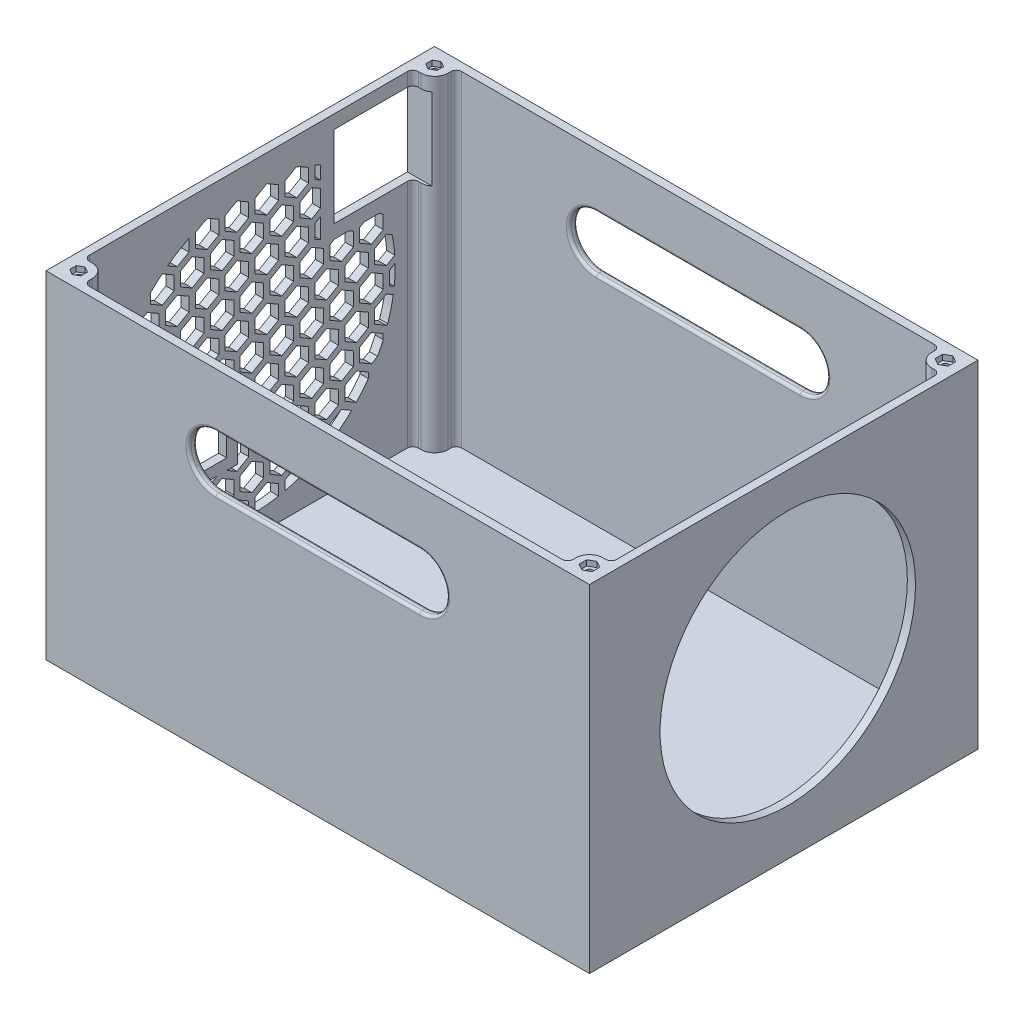
SolidWorks part; units mm, degrees
ref_plane "Front Plane" through (0, 0, 0) normal (0, 0, 1) x (1, 0, 0)
ref_plane "Top Plane" through (0, 0, 0) normal (0, 1, 0) x (1, 0, 0)
ref_plane "Right Plane" through (0, 0, 0) normal (1, 0, 0) x (0, 0, -1)
sketch "Sketch1" plane through (0, 0, 0) normal (0, 0, 1) x (1, 0, 0)
  line L1 (0, 0) -> (254, 0)
  line L2 (0, 0) -> (0, 152.4)
  line L3 (0, 152.4) -> (254, 152.4)
  line L4 (254, 0) -> (254, 152.4)
  dimension "D1" = 152.4
  dimension "D2" = 254
extrude "Boss-Extrude1" add sketch "Sketch1" along normal blind 3.81
sketch "Sketch2" plane through (0, 152.4, 0) normal (0, 1, 0) x (1, 0, 0)
  line L0 (254, 0) -> (0, 0) construction
  line L1 (0, -3.81) -> (0, 0) construction
  line L4 (127, 0) -> (127, -8.0453) construction
  line L11 (13.97, -7.62) -> (13.97, 0)
  line L12 (13.97, 0) -> (2.54, 0)
  line L14 (7.62, -13.97) -> (2.54, -13.97)
  line L21 (2.54, 0) -> (0, 0)
  line L22 (0, 0) -> (0, -13.97)
  line L23 (0, -13.97) -> (2.54, -13.97)
  line L24 (254, -13.97) -> (251.46, -13.97)
  line L25 (254, 0) -> (254, -13.97)
  line L26 (254, 0) -> (240.03, 0)
  line L27 (246.38, -13.97) -> (251.46, -13.97)
  line L29 (240.03, -7.62) -> (240.03, 0)
  circle A0 centre (7.62, -7.62) radius 1.5875
  arc A4 (7.62, -13.97) -> (13.97, -7.62) centre (7.62, -7.62) ccw
  arc A7 (246.38, -13.97) -> (240.03, -7.62) centre (246.38, -7.62) cw
  circle A8 centre (246.38, -7.62) radius 1.5875
  dimension "D1" = 3.175
  dimension "D2" = 7.62
  dimension "D3" = 7.62
  dimension "D4" = 12.7
extrude "Boss-Extrude2" add sketch "Sketch2" against normal through all
sketch "Sketch4" plane through (0, 0, 3.81) normal (0, 0, 1) x (1, 0, 0)
  line L5 (13.97, 0) -> (240.03, 0) construction
  line L10 (0, 152.4) -> (3.81, 152.4)
  line L11 (0, 152.4) -> (0, 0)
  line L12 (0, 0) -> (3.81, 0)
  line L13 (3.81, 152.4) -> (3.81, 0)
  line L15 (254, 152.4) -> (250.19, 152.4)
  line L16 (254, 152.4) -> (254, 0)
  line L17 (254, 0) -> (250.19, 0)
  line L18 (250.19, 152.4) -> (250.19, 0)
  dimension "D1" = 3.81
  dimension "D2" = 3.81
extrude "Boss-Extrude3" add sketch "Sketch4" along normal blind 177.8
sketch "Sketch3" plane through (0, 152.4, 0) normal (0, 1, 0) x (1, 0, 0)
  line L0 (127, 0) -> (127, -10.4452) construction
  line L1 (254, 0) -> (0, 0) construction
  circle A0 centre (7.62, -7.62) radius 1.7145
  circle A1 centre (246.38, -7.62) radius 1.7145
  dimension "D1" = 3.429
  dimension "D2" = 3.429
extrude "Cut-Extrude1" cut sketch "Sketch3" against normal through all
sketch "Sketch5" plane through (3.81, 0, 0) normal (1, 0, 0) x (0, 0, -1)
  line L5 (-181.61, 0) -> (-13.97, 0) construction
  line L6 (-181.61, 152.4) -> (-177.8, 152.4)
  line L7 (-181.61, 152.4) -> (-181.61, 0)
  line L8 (-181.61, 0) -> (-177.8, 0)
  line L9 (-177.8, 152.4) -> (-177.8, 0)
  dimension "D1" = 3.81
extrude "Boss-Extrude4" add sketch "Sketch5" along normal blind 248.92
sketch "Sketch6" plane through (0, 152.4, 0) normal (0, 1, 0) x (1, 0, 0)
  line L1 (7.62, -167.64) -> (0, -167.64)
  line L2 (0, -181.61) -> (0, 0) construction
  line L3 (127, -181.61) -> (127, -160.2672) construction
  line L4 (240.03, -181.61) -> (240.03, -173.99)
  line L5 (0, -167.64) -> (0, -181.61)
  line L6 (0, -181.61) -> (13.97, -181.61)
  line L7 (254, -181.61) -> (0, -181.61) construction
  line L8 (13.97, -181.61) -> (13.97, -173.99)
  line L9 (254, -181.61) -> (240.03, -181.61)
  line L10 (254, -167.64) -> (254, -181.61)
  line L11 (246.38, -167.64) -> (254, -167.64)
  circle A0 centre (7.62, -173.99) radius 1.5875
  arc A2 (13.97, -173.99) -> (7.62, -167.64) centre (7.62, -173.99) ccw
  arc A5 (240.03, -173.99) -> (246.38, -167.64) centre (246.38, -173.99) cw
  circle A6 centre (246.38, -173.99) radius 1.5875
  dimension "D1" = 7.62
  dimension "D2" = 7.62
  dimension "D3" = 3.175
  dimension "D4" = 12.7
extrude "Boss-Extrude5" add sketch "Sketch6" against normal through all
sketch "Sketch8" plane through (254, 0, 0) normal (1, 0, 0) x (0, 0, -1)
  line L1 (-181.61, 0) -> (0, 0) construction
  line L2 (0, 0) -> (0, 152.4) construction
  circle A0 centre (-88.9, 76.2) radius 59.69
  dimension "D1" = 119.38
  dimension "D2" = 76.2
  dimension "D3" = 88.9
extrude "Cut-Extrude3" cut sketch "Sketch8" against normal blind 5.08
sketch "Sketch9" plane through (0, 0, 0) normal (-1, 0, 0) x (0, 0, 1)
  line L1 (0, 152.4) -> (0, 0) construction
  line L14 (54.2537, 127.1602) -> (59.7529, 130.3352)
  line L15 (59.7529, 130.3352) -> (59.7529, 136.1667)
  line L19 (49.4362, 129.9416) -> (54.2537, 127.1602)
  line L20 (68.2237, 127.1602) -> (73.7229, 130.3352)
  line L21 (73.7229, 130.3352) -> (73.7229, 136.6852)
  line L22 (73.7229, 136.6852) -> (68.5258, 139.6858)
  line L23 (67.0955, 139.2089) -> (62.7244, 136.6852)
  line L24 (62.7244, 136.6852) -> (62.7244, 130.3352)
  line L25 (62.7244, 130.3352) -> (68.2237, 127.1602)
  line L26 (82.1937, 127.1602) -> (87.6929, 130.3352)
  line L27 (87.6929, 130.3352) -> (87.6929, 136.6852)
  line L28 (87.6929, 136.6852) -> (82.1937, 139.8602)
  line L29 (82.1937, 139.8602) -> (76.6944, 136.6852)
  line L30 (76.6944, 136.6852) -> (76.6944, 130.3352)
  line L31 (76.6944, 130.3352) -> (82.1937, 127.1602)
  line L32 (96.1637, 127.1602) -> (101.6629, 130.3352)
  line L33 (101.6629, 130.3352) -> (101.6629, 136.6852)
  line L34 (101.6629, 136.6852) -> (96.1637, 139.8602)
  line L35 (96.1637, 139.8602) -> (90.6644, 136.6852)
  line L36 (90.6644, 136.6852) -> (90.6644, 130.3352)
  line L37 (90.6644, 130.3352) -> (96.1637, 127.1602)
  line L38 (110.1337, 127.1602) -> (115.6329, 130.3352)
  line L39 (115.6329, 130.3352) -> (115.6329, 136.6852)
  line L40 (115.6329, 136.6852) -> (112.1801, 138.6787)
  line L41 (109.6312, 139.5701) -> (104.6344, 136.6852)
  line L42 (104.6344, 136.6852) -> (104.6344, 130.3352)
  line L43 (104.6344, 130.3352) -> (110.1337, 127.1602)
  line L44 (124.1037, 127.1602) -> (128.6085, 129.7611)
  line L48 (118.6044, 135.8926) -> (118.6044, 130.3352)
  line L49 (118.6044, 130.3352) -> (124.1037, 127.1602)
  line L80 (35.777, 116.4927) -> (38.7979, 118.2369)
  line L81 (38.7979, 118.2369) -> (38.7979, 120.1925)
  line L86 (47.2687, 115.0619) -> (52.7679, 118.2369)
  line L87 (52.7679, 118.2369) -> (52.7679, 124.5869)
  line L88 (52.7679, 124.5869) -> (47.2687, 127.7619)
  line L89 (47.2687, 127.7619) -> (45.2349, 126.5877)
  line L90 (41.7694, 123.3621) -> (41.7694, 118.2369)
  line L91 (41.7694, 118.2369) -> (47.2687, 115.0619)
  line L92 (61.2387, 115.0619) -> (66.7379, 118.2369)
  line L93 (66.7379, 118.2369) -> (66.7379, 124.5869)
  line L94 (66.7379, 124.5869) -> (61.2387, 127.7619)
  line L95 (61.2387, 127.7619) -> (55.7394, 124.5869)
  line L96 (55.7394, 124.5869) -> (55.7394, 118.2369)
  line L97 (55.7394, 118.2369) -> (61.2387, 115.0619)
  line L98 (75.2087, 115.0619) -> (80.7079, 118.2369)
  line L99 (80.7079, 118.2369) -> (80.7079, 124.5869)
  line L100 (80.7079, 124.5869) -> (75.2087, 127.7619)
  line L101 (75.2087, 127.7619) -> (69.7094, 124.5869)
  line L102 (69.7094, 124.5869) -> (69.7094, 118.2369)
  line L103 (69.7094, 118.2369) -> (75.2087, 115.0619)
  line L104 (89.1787, 115.0619) -> (94.6779, 118.2369)
  line L105 (94.6779, 118.2369) -> (94.6779, 124.5869)
  line L106 (94.6779, 124.5869) -> (89.1787, 127.7619)
  line L107 (89.1787, 127.7619) -> (83.6794, 124.5869)
  line L108 (83.6794, 124.5869) -> (83.6794, 118.2369)
  line L109 (83.6794, 118.2369) -> (89.1787, 115.0619)
  line L110 (103.1487, 115.0619) -> (108.6479, 118.2369)
  line L111 (108.6479, 118.2369) -> (108.6479, 124.5869)
  line L112 (108.6479, 124.5869) -> (103.1487, 127.7619)
  line L113 (103.1487, 127.7619) -> (97.6494, 124.5869)
  line L114 (97.6494, 124.5869) -> (97.6494, 118.2369)
  line L115 (97.6494, 118.2369) -> (103.1487, 115.0619)
  line L116 (117.1187, 115.0619) -> (122.6179, 118.2369)
  line L117 (122.6179, 118.2369) -> (122.6179, 124.5869)
  line L118 (122.6179, 124.5869) -> (117.1187, 127.7619)
  line L119 (117.1187, 127.7619) -> (111.6194, 124.5869)
  line L120 (111.6194, 124.5869) -> (111.6194, 118.2369)
  line L121 (111.6194, 118.2369) -> (117.1187, 115.0619)
  line L122 (131.0887, 115.0619) -> (136.5879, 118.2369)
  line L123 (136.5879, 118.2369) -> (136.5879, 122.7984)
  line L124 (131.3681, 127.6005) -> (131.0887, 127.7619)
  line L125 (131.0887, 127.7619) -> (125.5894, 124.5869)
  line L126 (125.5894, 124.5869) -> (125.5894, 118.2369)
  line L127 (125.5894, 118.2369) -> (131.0887, 115.0619)
  line L132 (139.5594, 119.5495) -> (139.5594, 118.2369)
  line L133 (139.5594, 118.2369) -> (141.5799, 117.0704)
  line L152 (28.3651, 104.1479) -> (31.8129, 106.1385)
  line L153 (31.8129, 106.1385) -> (31.8129, 110.6474)
  line L158 (40.2837, 102.9635) -> (45.7829, 106.1385)
  line L159 (45.7829, 106.1385) -> (45.7829, 112.4885)
  line L160 (45.7829, 112.4885) -> (40.2837, 115.6635)
  line L161 (40.2837, 115.6635) -> (34.7844, 112.4885)
  line L162 (34.7844, 112.4885) -> (34.7844, 106.1385)
  line L163 (34.7844, 106.1385) -> (40.2837, 102.9635)
  line L164 (54.2537, 102.9635) -> (59.7529, 106.1385)
  line L165 (59.7529, 106.1385) -> (59.7529, 112.4885)
  line L166 (59.7529, 112.4885) -> (54.2537, 115.6635)
  line L167 (54.2537, 115.6635) -> (48.7544, 112.4885)
  line L168 (48.7544, 112.4885) -> (48.7544, 106.1385)
  line L169 (48.7544, 106.1385) -> (54.2537, 102.9635)
  line L170 (68.2237, 102.9635) -> (73.7229, 106.1385)
  line L171 (73.7229, 106.1385) -> (73.7229, 112.4885)
  line L172 (73.7229, 112.4885) -> (68.2237, 115.6635)
  line L173 (68.2237, 115.6635) -> (62.7244, 112.4885)
  line L174 (62.7244, 112.4885) -> (62.7244, 106.1385)
  line L175 (62.7244, 106.1385) -> (68.2237, 102.9635)
  line L176 (82.1937, 102.9635) -> (87.6929, 106.1385)
  line L177 (87.6929, 106.1385) -> (87.6929, 112.4885)
  line L178 (87.6929, 112.4885) -> (82.1937, 115.6635)
  line L179 (82.1937, 115.6635) -> (76.6944, 112.4885)
  line L180 (76.6944, 112.4885) -> (76.6944, 106.1385)
  line L181 (76.6944, 106.1385) -> (82.1937, 102.9635)
  line L182 (96.1637, 102.9635) -> (101.6629, 106.1385)
  line L183 (101.6629, 106.1385) -> (101.6629, 112.4885)
  line L184 (101.6629, 112.4885) -> (96.1637, 115.6635)
  line L185 (96.1637, 115.6635) -> (90.6644, 112.4885)
  line L186 (90.6644, 112.4885) -> (90.6644, 106.1385)
  line L187 (90.6644, 106.1385) -> (96.1637, 102.9635)
  line L188 (110.1337, 102.9635) -> (115.6329, 106.1385)
  line L189 (115.6329, 106.1385) -> (115.6329, 112.4885)
  line L190 (115.6329, 112.4885) -> (110.1337, 115.6635)
  line L191 (110.1337, 115.6635) -> (104.6344, 112.4885)
  line L192 (104.6344, 112.4885) -> (104.6344, 106.1385)
  line L193 (104.6344, 106.1385) -> (110.1337, 102.9635)
  line L194 (124.1037, 102.9635) -> (129.6029, 106.1385)
  line L195 (129.6029, 106.1385) -> (129.6029, 112.4885)
  line L196 (129.6029, 112.4885) -> (124.1037, 115.6635)
  line L197 (124.1037, 115.6635) -> (118.6044, 112.4885)
  line L198 (118.6044, 112.4885) -> (118.6044, 106.1385)
  line L199 (118.6044, 106.1385) -> (124.1037, 102.9635)
  line L200 (138.0737, 102.9635) -> (143.5729, 106.1385)
  line L201 (143.5729, 106.1385) -> (143.5729, 112.4885)
  line L202 (143.5729, 112.4885) -> (138.0737, 115.6635)
  line L203 (138.0737, 115.6635) -> (132.5744, 112.4885)
  line L204 (132.5744, 112.4885) -> (132.5744, 106.1385)
  line L205 (132.5744, 106.1385) -> (138.0737, 102.9635)
  line L210 (146.5444, 109.7064) -> (146.5444, 106.1385)
  line L211 (146.5444, 106.1385) -> (149.2297, 104.5882)
  line L224 (24.6234, 93.922) -> (24.8279, 94.0401)
  line L225 (24.8279, 94.0401) -> (24.8279, 94.648)
  line L230 (33.2987, 90.8651) -> (38.7979, 94.0401)
  line L231 (38.7979, 94.0401) -> (38.7979, 100.3901)
  line L232 (38.7979, 100.3901) -> (33.2987, 103.5651)
  line L233 (33.2987, 103.5651) -> (27.7994, 100.3901)
  line L234 (27.7994, 100.3901) -> (27.7994, 94.0401)
  line L235 (27.7994, 94.0401) -> (33.2987, 90.8651)
  line L236 (47.2687, 90.8651) -> (52.7679, 94.0401)
  line L237 (52.7679, 94.0401) -> (52.7679, 100.3901)
  line L238 (52.7679, 100.3901) -> (47.2687, 103.5651)
  line L239 (47.2687, 103.5651) -> (41.7694, 100.3901)
  line L240 (41.7694, 100.3901) -> (41.7694, 94.0401)
  line L241 (41.7694, 94.0401) -> (47.2687, 90.8651)
  line L242 (61.2387, 90.8651) -> (66.7379, 94.0401)
  line L243 (66.7379, 94.0401) -> (66.7379, 100.3901)
  line L244 (66.7379, 100.3901) -> (61.2387, 103.5651)
  line L245 (61.2387, 103.5651) -> (55.7394, 100.3901)
  line L246 (55.7394, 100.3901) -> (55.7394, 94.0401)
  line L247 (55.7394, 94.0401) -> (61.2387, 90.8651)
  line L248 (75.2087, 90.8651) -> (80.7079, 94.0401)
  line L249 (80.7079, 94.0401) -> (80.7079, 100.3901)
  line L250 (80.7079, 100.3901) -> (75.2087, 103.5651)
  line L251 (75.2087, 103.5651) -> (69.7094, 100.3901)
  line L252 (69.7094, 100.3901) -> (69.7094, 94.0401)
  line L253 (69.7094, 94.0401) -> (75.2087, 90.8651)
  line L254 (89.1787, 90.8651) -> (94.6779, 94.0401)
  line L255 (94.6779, 94.0401) -> (94.6779, 100.3901)
  line L256 (94.6779, 100.3901) -> (89.1787, 103.5651)
  line L257 (89.1787, 103.5651) -> (83.6794, 100.3901)
  line L258 (83.6794, 100.3901) -> (83.6794, 94.0401)
  line L259 (83.6794, 94.0401) -> (89.1787, 90.8651)
  line L260 (103.1487, 90.8651) -> (108.6479, 94.0401)
  line L261 (108.6479, 94.0401) -> (108.6479, 100.3901)
  line L262 (108.6479, 100.3901) -> (103.1487, 103.5651)
  line L263 (103.1487, 103.5651) -> (97.6494, 100.3901)
  line L264 (97.6494, 100.3901) -> (97.6494, 94.0401)
  line L265 (97.6494, 94.0401) -> (103.1487, 90.8651)
  line L266 (117.1187, 90.8651) -> (122.6179, 94.0401)
  line L267 (122.6179, 94.0401) -> (122.6179, 100.3901)
  line L268 (122.6179, 100.3901) -> (117.1187, 103.5651)
  line L269 (117.1187, 103.5651) -> (111.6194, 100.3901)
  line L270 (111.6194, 100.3901) -> (111.6194, 94.0401)
  line L271 (111.6194, 94.0401) -> (117.1187, 90.8651)
  line L272 (131.0887, 90.8651) -> (136.5879, 94.0401)
  line L273 (136.5879, 94.0401) -> (136.5879, 100.3901)
  line L274 (136.5879, 100.3901) -> (131.0887, 103.5651)
  line L275 (131.0887, 103.5651) -> (125.5894, 100.3901)
  line L276 (125.5894, 100.3901) -> (125.5894, 94.0401)
  line L277 (125.5894, 94.0401) -> (131.0887, 90.8651)
  line L278 (145.0587, 90.8651) -> (150.5579, 94.0401)
  line L279 (150.5579, 94.0401) -> (150.5579, 100.3901)
  line L280 (150.5579, 100.3901) -> (145.0587, 103.5651)
  line L281 (145.0587, 103.5651) -> (139.5594, 100.3901)
  line L282 (139.5594, 100.3901) -> (139.5594, 94.0401)
  line L283 (139.5594, 94.0401) -> (145.0587, 90.8651)
  line L302 (26.3137, 78.7667) -> (31.8129, 81.9417)
  line L303 (31.8129, 81.9417) -> (31.8129, 88.2917)
  line L304 (31.8129, 88.2917) -> (26.3137, 91.4667)
  line L305 (26.3137, 91.4667) -> (23.6543, 89.9313)
  line L307 (22.3999, 81.0264) -> (26.3137, 78.7667)
  line L308 (40.2837, 78.7667) -> (45.7829, 81.9417)
  line L309 (45.7829, 81.9417) -> (45.7829, 88.2917)
  line L310 (45.7829, 88.2917) -> (40.2837, 91.4667)
  line L311 (40.2837, 91.4667) -> (34.7844, 88.2917)
  line L312 (34.7844, 88.2917) -> (34.7844, 81.9417)
  line L313 (34.7844, 81.9417) -> (40.2837, 78.7667)
  line L314 (54.2537, 78.7667) -> (59.7529, 81.9417)
  line L315 (59.7529, 81.9417) -> (59.7529, 88.2917)
  line L316 (59.7529, 88.2917) -> (54.2537, 91.4667)
  line L317 (54.2537, 91.4667) -> (48.7544, 88.2917)
  line L318 (48.7544, 88.2917) -> (48.7544, 81.9417)
  line L319 (48.7544, 81.9417) -> (54.2537, 78.7667)
  line L320 (68.2237, 78.7667) -> (73.7229, 81.9417)
  line L321 (73.7229, 81.9417) -> (73.7229, 88.2917)
  line L322 (73.7229, 88.2917) -> (68.2237, 91.4667)
  line L323 (68.2237, 91.4667) -> (62.7244, 88.2917)
  line L324 (62.7244, 88.2917) -> (62.7244, 81.9417)
  line L325 (62.7244, 81.9417) -> (68.2237, 78.7667)
  line L326 (82.1937, 78.7667) -> (87.6929, 81.9417)
  line L327 (87.6929, 81.9417) -> (87.6929, 88.2917)
  line L328 (87.6929, 88.2917) -> (82.1937, 91.4667)
  line L329 (82.1937, 91.4667) -> (76.6944, 88.2917)
  line L330 (76.6944, 88.2917) -> (76.6944, 81.9417)
  line L331 (76.6944, 81.9417) -> (82.1937, 78.7667)
  line L332 (96.1637, 78.7667) -> (101.6629, 81.9417)
  line L333 (101.6629, 81.9417) -> (101.6629, 88.2917)
  line L334 (101.6629, 88.2917) -> (96.1637, 91.4667)
  line L335 (96.1637, 91.4667) -> (90.6644, 88.2917)
  line L336 (90.6644, 88.2917) -> (90.6644, 81.9417)
  line L337 (90.6644, 81.9417) -> (96.1637, 78.7667)
  line L338 (110.1337, 78.7667) -> (115.6329, 81.9417)
  line L339 (115.6329, 81.9417) -> (115.6329, 88.2917)
  line L340 (115.6329, 88.2917) -> (110.1337, 91.4667)
  line L341 (110.1337, 91.4667) -> (104.6344, 88.2917)
  line L342 (104.6344, 88.2917) -> (104.6344, 81.9417)
  line L343 (104.6344, 81.9417) -> (110.1337, 78.7667)
  line L344 (124.1037, 78.7667) -> (129.6029, 81.9417)
  line L345 (129.6029, 81.9417) -> (129.6029, 88.2917)
  line L346 (129.6029, 88.2917) -> (124.1037, 91.4667)
  line L347 (124.1037, 91.4667) -> (118.6044, 88.2917)
  line L348 (118.6044, 88.2917) -> (118.6044, 81.9417)
  line L349 (118.6044, 81.9417) -> (124.1037, 78.7667)
  line L350 (138.0737, 78.7667) -> (143.5729, 81.9417)
  line L351 (143.5729, 81.9417) -> (143.5729, 88.2917)
  line L352 (143.5729, 88.2917) -> (138.0737, 91.4667)
  line L353 (138.0737, 91.4667) -> (132.5744, 88.2917)
  line L354 (132.5744, 88.2917) -> (132.5744, 81.9417)
  line L355 (132.5744, 81.9417) -> (138.0737, 78.7667)
  line L356 (152.0437, 78.7667) -> (155.4218, 80.7171)
  line L358 (154.0674, 90.2983) -> (152.0437, 91.4667)
  line L359 (152.0437, 91.4667) -> (146.5444, 88.2917)
  line L360 (146.5444, 88.2917) -> (146.5444, 81.9417)
  line L361 (146.5444, 81.9417) -> (152.0437, 78.7667)
  line L374 (22.6605, 68.592) -> (24.8279, 69.8434)
  line L375 (24.8279, 69.8434) -> (24.8279, 76.1934)
  line L376 (24.8279, 76.1934) -> (22.2416, 77.6866)
  line L380 (33.2987, 66.6684) -> (38.7979, 69.8434)
  line L381 (38.7979, 69.8434) -> (38.7979, 76.1934)
  line L382 (38.7979, 76.1934) -> (33.2987, 79.3684)
  line L383 (33.2987, 79.3684) -> (27.7994, 76.1934)
  line L384 (27.7994, 76.1934) -> (27.7994, 69.8434)
  line L385 (27.7994, 69.8434) -> (33.2987, 66.6684)
  line L386 (47.2687, 66.6684) -> (52.7679, 69.8434)
  line L387 (52.7679, 69.8434) -> (52.7679, 76.1934)
  line L388 (52.7679, 76.1934) -> (47.2687, 79.3684)
  line L389 (47.2687, 79.3684) -> (41.7694, 76.1934)
  line L390 (41.7694, 76.1934) -> (41.7694, 69.8434)
  line L391 (41.7694, 69.8434) -> (47.2687, 66.6684)
  line L392 (61.2387, 66.6684) -> (66.7379, 69.8434)
  line L393 (66.7379, 69.8434) -> (66.7379, 76.1934)
  line L394 (66.7379, 76.1934) -> (61.2387, 79.3684)
  line L395 (61.2387, 79.3684) -> (55.7394, 76.1934)
  line L396 (55.7394, 76.1934) -> (55.7394, 69.8434)
  line L397 (55.7394, 69.8434) -> (61.2387, 66.6684)
  line L398 (75.2087, 66.6684) -> (80.7079, 69.8434)
  line L399 (80.7079, 69.8434) -> (80.7079, 76.1934)
  line L400 (80.7079, 76.1934) -> (75.2087, 79.3684)
  line L401 (75.2087, 79.3684) -> (69.7094, 76.1934)
  line L402 (69.7094, 76.1934) -> (69.7094, 69.8434)
  line L403 (69.7094, 69.8434) -> (75.2087, 66.6684)
  line L404 (89.1787, 66.6684) -> (94.6779, 69.8434)
  line L405 (94.6779, 69.8434) -> (94.6779, 76.1934)
  line L406 (94.6779, 76.1934) -> (89.1787, 79.3684)
  line L407 (89.1787, 79.3684) -> (83.6794, 76.1934)
  line L408 (83.6794, 76.1934) -> (83.6794, 69.8434)
  line L409 (83.6794, 69.8434) -> (89.1787, 66.6684)
  line L410 (103.1487, 66.6684) -> (108.6479, 69.8434)
  line L411 (108.6479, 69.8434) -> (108.6479, 76.1934)
  line L412 (108.6479, 76.1934) -> (103.1487, 79.3684)
  line L413 (103.1487, 79.3684) -> (97.6494, 76.1934)
  line L414 (97.6494, 76.1934) -> (97.6494, 69.8434)
  line L415 (97.6494, 69.8434) -> (103.1487, 66.6684)
  line L416 (117.1187, 66.6684) -> (122.6179, 69.8434)
  line L417 (122.6179, 69.8434) -> (122.6179, 76.1934)
  line L418 (122.6179, 76.1934) -> (117.1187, 79.3684)
  line L419 (117.1187, 79.3684) -> (111.6194, 76.1934)
  line L420 (111.6194, 76.1934) -> (111.6194, 69.8434)
  line L421 (111.6194, 69.8434) -> (117.1187, 66.6684)
  line L422 (131.0887, 66.6684) -> (136.5879, 69.8434)
  line L423 (136.5879, 69.8434) -> (136.5879, 76.1934)
  line L424 (136.5879, 76.1934) -> (131.0887, 79.3684)
  line L425 (131.0887, 79.3684) -> (125.5894, 76.1934)
  line L426 (125.5894, 76.1934) -> (125.5894, 69.8434)
  line L427 (125.5894, 69.8434) -> (131.0887, 66.6684)
  line L428 (145.0587, 66.6684) -> (150.5579, 69.8434)
  line L429 (150.5579, 69.8434) -> (150.5579, 76.1934)
  line L430 (150.5579, 76.1934) -> (145.0587, 79.3684)
  line L431 (145.0587, 79.3684) -> (139.5594, 76.1934)
  line L432 (139.5594, 76.1934) -> (139.5594, 69.8434)
  line L433 (139.5594, 69.8434) -> (145.0587, 66.6684)
  line L437 (155.5648, 77.3685) -> (153.5294, 76.1934)
  line L438 (153.5294, 76.1934) -> (153.5294, 69.8434)
  line L439 (153.5294, 69.8434) -> (155.1735, 68.8941)
  line L452 (26.3137, 54.57) -> (31.8129, 57.745)
  line L453 (31.8129, 57.745) -> (31.8129, 64.095)
  line L454 (31.8129, 64.095) -> (26.3137, 67.27)
  line L455 (26.3137, 67.27) -> (23.1028, 65.4162)
  line L457 (25.7132, 54.9167) -> (26.3137, 54.57)
  line L458 (40.2837, 54.57) -> (45.7829, 57.745)
  line L459 (45.7829, 57.745) -> (45.7829, 64.095)
  line L460 (45.7829, 64.095) -> (40.2837, 67.27)
  line L461 (40.2837, 67.27) -> (34.7844, 64.095)
  line L462 (34.7844, 64.095) -> (34.7844, 57.745)
  line L463 (34.7844, 57.745) -> (40.2837, 54.57)
  line L464 (54.2537, 54.57) -> (59.7529, 57.745)
  line L465 (59.7529, 57.745) -> (59.7529, 64.095)
  line L466 (59.7529, 64.095) -> (54.2537, 67.27)
  line L467 (54.2537, 67.27) -> (48.7544, 64.095)
  line L468 (48.7544, 64.095) -> (48.7544, 57.745)
  line L469 (48.7544, 57.745) -> (54.2537, 54.57)
  line L470 (68.2237, 54.57) -> (73.7229, 57.745)
  line L471 (73.7229, 57.745) -> (73.7229, 64.095)
  line L472 (73.7229, 64.095) -> (68.2237, 67.27)
  line L473 (68.2237, 67.27) -> (62.7244, 64.095)
  line L474 (62.7244, 64.095) -> (62.7244, 57.745)
  line L475 (62.7244, 57.745) -> (68.2237, 54.57)
  line L476 (82.1937, 54.57) -> (87.6929, 57.745)
  line L477 (87.6929, 57.745) -> (87.6929, 64.095)
  line L478 (87.6929, 64.095) -> (82.1937, 67.27)
  line L479 (82.1937, 67.27) -> (76.6944, 64.095)
  line L480 (76.6944, 64.095) -> (76.6944, 57.745)
  line L481 (76.6944, 57.745) -> (82.1937, 54.57)
  line L482 (96.1637, 54.57) -> (101.6629, 57.745)
  line L483 (101.6629, 57.745) -> (101.6629, 64.095)
  line L484 (101.6629, 64.095) -> (96.1637, 67.27)
  line L485 (96.1637, 67.27) -> (90.6644, 64.095)
  line L486 (90.6644, 64.095) -> (90.6644, 57.745)
  line L487 (90.6644, 57.745) -> (96.1637, 54.57)
  line L488 (110.1337, 54.57) -> (115.6329, 57.745)
  line L489 (115.6329, 57.745) -> (115.6329, 64.095)
  line L490 (115.6329, 64.095) -> (110.1337, 67.27)
  line L491 (110.1337, 67.27) -> (104.6344, 64.095)
  line L492 (104.6344, 64.095) -> (104.6344, 57.745)
  line L493 (104.6344, 57.745) -> (110.1337, 54.57)
  line L494 (124.1037, 54.57) -> (129.6029, 57.745)
  line L495 (129.6029, 57.745) -> (129.6029, 64.095)
  line L496 (129.6029, 64.095) -> (124.1037, 67.27)
  line L497 (124.1037, 67.27) -> (118.6044, 64.095)
  line L498 (118.6044, 64.095) -> (118.6044, 57.745)
  line L499 (118.6044, 57.745) -> (124.1037, 54.57)
  line L500 (138.0737, 54.57) -> (143.5729, 57.745)
  line L501 (143.5729, 57.745) -> (143.5729, 64.095)
  line L502 (143.5729, 64.095) -> (138.0737, 67.27)
  line L503 (138.0737, 67.27) -> (132.5744, 64.095)
  line L504 (132.5744, 64.095) -> (132.5744, 57.745)
  line L505 (132.5744, 57.745) -> (138.0737, 54.57)
  line L508 (154.7447, 65.7105) -> (152.0437, 67.27)
  line L509 (152.0437, 67.27) -> (146.5444, 64.095)
  line L510 (146.5444, 64.095) -> (146.5444, 57.745)
  line L511 (146.5444, 57.745) -> (152.0437, 54.57)
  line L530 (33.2987, 42.4716) -> (38.7979, 45.6466)
  line L531 (38.7979, 45.6466) -> (38.7979, 51.9966)
  line L532 (38.7979, 51.9966) -> (33.2987, 55.1716)
  line L533 (33.2987, 55.1716) -> (27.7994, 51.9966)
  line L534 (27.7994, 51.9966) -> (27.7994, 49.5115)
  line L535 (30.4526, 44.1148) -> (33.2987, 42.4716)
  line L536 (47.2687, 42.4716) -> (52.7679, 45.6466)
  line L537 (52.7679, 45.6466) -> (52.7679, 51.9966)
  line L538 (52.7679, 51.9966) -> (47.2687, 55.1716)
  line L539 (47.2687, 55.1716) -> (41.7694, 51.9966)
  line L540 (41.7694, 51.9966) -> (41.7694, 45.6466)
  line L541 (41.7694, 45.6466) -> (47.2687, 42.4716)
  line L542 (61.2387, 42.4716) -> (66.7379, 45.6466)
  line L543 (66.7379, 45.6466) -> (66.7379, 51.9966)
  line L544 (66.7379, 51.9966) -> (61.2387, 55.1716)
  line L545 (61.2387, 55.1716) -> (55.7394, 51.9966)
  line L546 (55.7394, 51.9966) -> (55.7394, 45.6466)
  line L547 (55.7394, 45.6466) -> (61.2387, 42.4716)
  line L548 (75.2087, 42.4716) -> (80.7079, 45.6466)
  line L549 (80.7079, 45.6466) -> (80.7079, 51.9966)
  line L550 (80.7079, 51.9966) -> (75.2087, 55.1716)
  line L551 (75.2087, 55.1716) -> (69.7094, 51.9966)
  line L552 (69.7094, 51.9966) -> (69.7094, 45.6466)
  line L553 (69.7094, 45.6466) -> (75.2087, 42.4716)
  line L554 (89.1787, 42.4716) -> (94.6779, 45.6466)
  line L555 (94.6779, 45.6466) -> (94.6779, 51.9966)
  line L556 (94.6779, 51.9966) -> (89.1787, 55.1716)
  line L557 (89.1787, 55.1716) -> (83.6794, 51.9966)
  line L558 (83.6794, 51.9966) -> (83.6794, 45.6466)
  line L559 (83.6794, 45.6466) -> (89.1787, 42.4716)
  line L560 (103.1487, 42.4716) -> (108.6479, 45.6466)
  line L561 (108.6479, 45.6466) -> (108.6479, 51.9966)
  line L562 (108.6479, 51.9966) -> (103.1487, 55.1716)
  line L563 (103.1487, 55.1716) -> (97.6494, 51.9966)
  line L564 (97.6494, 51.9966) -> (97.6494, 45.6466)
  line L565 (97.6494, 45.6466) -> (103.1487, 42.4716)
  line L566 (117.1187, 42.4716) -> (122.6179, 45.6466)
  line L567 (122.6179, 45.6466) -> (122.6179, 51.9966)
  line L568 (122.6179, 51.9966) -> (117.1187, 55.1716)
  line L569 (117.1187, 55.1716) -> (111.6194, 51.9966)
  line L570 (111.6194, 51.9966) -> (111.6194, 45.6466)
  line L571 (111.6194, 45.6466) -> (117.1187, 42.4716)
  line L572 (131.0887, 42.4716) -> (136.5879, 45.6466)
  line L573 (136.5879, 45.6466) -> (136.5879, 51.9966)
  line L574 (136.5879, 51.9966) -> (131.0887, 55.1716)
  line L575 (131.0887, 55.1716) -> (125.5894, 51.9966)
  line L576 (125.5894, 51.9966) -> (125.5894, 45.6466)
  line L577 (125.5894, 45.6466) -> (131.0887, 42.4716)
  line L578 (145.0587, 42.4716) -> (147.0851, 43.6416)
  line L579 (150.5579, 50.8257) -> (150.5579, 51.9966)
  line L580 (150.5579, 51.9966) -> (145.0587, 55.1716)
  line L581 (145.0587, 55.1716) -> (139.5594, 51.9966)
  line L582 (139.5594, 51.9966) -> (139.5594, 45.6466)
  line L583 (139.5594, 45.6466) -> (145.0587, 42.4716)
  line L608 (40.2837, 30.3732) -> (45.7829, 33.5482)
  line L609 (45.7829, 33.5482) -> (45.7829, 39.8982)
  line L610 (45.7829, 39.8982) -> (40.2837, 43.0732)
  line L611 (40.2837, 43.0732) -> (34.7844, 39.8982)
  line L612 (34.7844, 39.8982) -> (34.7844, 37.2505)
  line L614 (54.2537, 30.3732) -> (59.7529, 33.5482)
  line L615 (59.7529, 33.5482) -> (59.7529, 39.8982)
  line L616 (59.7529, 39.8982) -> (54.2537, 43.0732)
  line L617 (54.2537, 43.0732) -> (48.7544, 39.8982)
  line L618 (48.7544, 39.8982) -> (48.7544, 33.5482)
  line L619 (48.7544, 33.5482) -> (54.2537, 30.3732)
  line L620 (68.2237, 30.3732) -> (73.7229, 33.5482)
  line L621 (73.7229, 33.5482) -> (73.7229, 39.8982)
  line L622 (73.7229, 39.8982) -> (68.2237, 43.0732)
  line L623 (68.2237, 43.0732) -> (62.7244, 39.8982)
  line L624 (62.7244, 39.8982) -> (62.7244, 33.5482)
  line L625 (62.7244, 33.5482) -> (68.2237, 30.3732)
  line L626 (82.1937, 30.3732) -> (87.6929, 33.5482)
  line L627 (87.6929, 33.5482) -> (87.6929, 39.8982)
  line L628 (87.6929, 39.8982) -> (82.1937, 43.0732)
  line L629 (82.1937, 43.0732) -> (76.6944, 39.8982)
  line L630 (76.6944, 39.8982) -> (76.6944, 33.5482)
  line L631 (76.6944, 33.5482) -> (82.1937, 30.3732)
  line L632 (96.1637, 30.3732) -> (101.6629, 33.5482)
  line L633 (101.6629, 33.5482) -> (101.6629, 39.8982)
  line L634 (101.6629, 39.8982) -> (96.1637, 43.0732)
  line L635 (96.1637, 43.0732) -> (90.6644, 39.8982)
  line L636 (90.6644, 39.8982) -> (90.6644, 33.5482)
  line L637 (90.6644, 33.5482) -> (96.1637, 30.3732)
  line L638 (110.1337, 30.3732) -> (115.6329, 33.5482)
  line L639 (115.6329, 33.5482) -> (115.6329, 39.8982)
  line L640 (115.6329, 39.8982) -> (110.1337, 43.0732)
  line L641 (110.1337, 43.0732) -> (104.6344, 39.8982)
  line L642 (104.6344, 39.8982) -> (104.6344, 33.5482)
  line L643 (104.6344, 33.5482) -> (110.1337, 30.3732)
  line L644 (124.1037, 30.3732) -> (129.6029, 33.5482)
  line L645 (129.6029, 33.5482) -> (129.6029, 39.8982)
  line L646 (129.6029, 39.8982) -> (124.1037, 43.0732)
  line L647 (124.1037, 43.0732) -> (118.6044, 39.8982)
  line L648 (118.6044, 39.8982) -> (118.6044, 33.5482)
  line L649 (118.6044, 33.5482) -> (124.1037, 30.3732)
  line L651 (143.5729, 38.0369) -> (143.5729, 39.8982)
  line L652 (143.5729, 39.8982) -> (138.0737, 43.0732)
  line L653 (138.0737, 43.0732) -> (132.5744, 39.8982)
  line L654 (132.5744, 39.8982) -> (132.5744, 33.5482)
  line L655 (132.5744, 33.5482) -> (137.5918, 30.6515)
  line L686 (51.7272, 20.849) -> (52.7679, 21.4499)
  line L687 (52.7679, 21.4499) -> (52.7679, 27.7999)
  line L688 (52.7679, 27.7999) -> (47.2687, 30.9749)
  line L689 (47.2687, 30.9749) -> (42.563, 28.258)
  line L692 (61.2387, 18.2749) -> (66.7379, 21.4499)
  line L693 (66.7379, 21.4499) -> (66.7379, 27.7999)
  line L694 (66.7379, 27.7999) -> (61.2387, 30.9749)
  line L695 (61.2387, 30.9749) -> (55.7394, 27.7999)
  line L696 (55.7394, 27.7999) -> (55.7394, 21.4499)
  line L697 (55.7394, 21.4499) -> (61.2387, 18.2749)
  line L698 (75.2087, 18.2749) -> (80.7079, 21.4499)
  line L699 (80.7079, 21.4499) -> (80.7079, 27.7999)
  line L700 (80.7079, 27.7999) -> (75.2087, 30.9749)
  line L701 (75.2087, 30.9749) -> (69.7094, 27.7999)
  line L702 (69.7094, 27.7999) -> (69.7094, 21.4499)
  line L703 (69.7094, 21.4499) -> (75.2087, 18.2749)
  line L704 (89.1787, 18.2749) -> (94.6779, 21.4499)
  line L705 (94.6779, 21.4499) -> (94.6779, 27.7999)
  line L706 (94.6779, 27.7999) -> (89.1787, 30.9749)
  line L707 (89.1787, 30.9749) -> (83.6794, 27.7999)
  line L708 (83.6794, 27.7999) -> (83.6794, 21.4499)
  line L709 (83.6794, 21.4499) -> (89.1787, 18.2749)
  line L710 (103.1487, 18.2749) -> (108.6479, 21.4499)
  line L711 (108.6479, 21.4499) -> (108.6479, 27.7999)
  line L712 (108.6479, 27.7999) -> (103.1487, 30.9749)
  line L713 (103.1487, 30.9749) -> (97.6494, 27.7999)
  line L714 (97.6494, 27.7999) -> (97.6494, 21.4499)
  line L715 (97.6494, 21.4499) -> (103.1487, 18.2749)
  line L716 (117.1187, 18.2749) -> (122.6179, 21.4499)
  line L717 (122.6179, 21.4499) -> (122.6179, 27.7999)
  line L718 (122.6179, 27.7999) -> (117.1187, 30.9749)
  line L719 (117.1187, 30.9749) -> (111.6194, 27.7999)
  line L720 (111.6194, 27.7999) -> (111.6194, 21.4499)
  line L721 (111.6194, 21.4499) -> (117.1187, 18.2749)
  line L724 (135.4449, 28.4598) -> (131.0887, 30.9749)
  line L725 (131.0887, 30.9749) -> (125.5894, 27.7999)
  line L726 (125.5894, 27.7999) -> (125.5894, 21.4499)
  line L727 (125.5894, 21.4499) -> (126.3298, 21.0224)
  line L771 (73.7229, 11.2753) -> (73.7229, 15.7015)
  line L772 (73.7229, 15.7015) -> (68.2237, 18.8765)
  line L773 (68.2237, 18.8765) -> (62.7244, 15.7015)
  line L774 (62.7244, 15.7015) -> (62.7244, 14.8779)
  line L777 (87.6929, 9.3515) -> (87.6929, 15.7015)
  line L778 (87.6929, 15.7015) -> (82.1937, 18.8765)
  line L779 (82.1937, 18.8765) -> (76.6944, 15.7015)
  line L780 (76.6944, 15.7015) -> (76.6944, 10.6517)
  line L783 (101.6629, 10.7579) -> (101.6629, 15.7015)
  line L784 (101.6629, 15.7015) -> (96.1637, 18.8765)
  line L785 (96.1637, 18.8765) -> (90.6644, 15.7015)
  line L786 (90.6644, 15.7015) -> (90.6644, 9.3515)
  line L789 (115.6329, 15.1189) -> (115.6329, 15.7015)
  line L790 (115.6329, 15.7015) -> (110.1337, 18.8765)
  line L791 (110.1337, 18.8765) -> (104.6344, 15.7015)
  line L792 (104.6344, 15.7015) -> (104.6344, 11.4082)
  circle A0 centre (88.9, 76.2) radius 66.675
  dimension "D2" = 88.9
  dimension "D3" = 133.35
extrude "Cut-Extrude4" cut sketch "Sketch9" against normal blind 5.08 contours L96 L97 L92 L93 L94 L95 | L15 A0 L19 L14 | L22 A0 L23 L24 L25 L20 L21 | L30 L31 L26 L27 L28 L29 | L36 L37 L32 L33 L34 L35 | L40 A0 L41 L42 L43 L38 L39 | L44 A0 L48 L49 | L123 A0 L124 L125 L126 L127 L122 | L120 L121 L116 L117 L118 L119 | L114 L115 L110 L111 L112 L113 | L108 L109 L104 L105 L106 L107 | L102 L103 L98 L99 L100 L101 | L89 A0 L90 L91 L86 L87 L88 | L162 L163 L158 L159 L160 L161 | L153 A0 L152 | L168 L169 L164 L165 L166 L167 | L174 L175 L170 L171 L172 L173 | L180 L181 L176 L177 L178 L179 | L186 L187 L182 L183 L184 L185 | L192 L193 L188 L189 L190 L191 | L198 L199 L194 L195 L196 L197 | L204 L205 L200 L201 L202 L203 | L211 A0 L210 | L282 L283 L278 L279 L280 L281 | L276 L277 L272 L273 L274 L275 | L264 L265 L260 L261 L262 L263 | L258 L259 L254 L255 L256 L257 | L252 L253 L248 L249 L250 L251 | L246 L247 L242 L243 L244 L245 | L240 L241 L236 L237 L238 L239 | L234 L235 L230 L231 L232 L233 | L270 L271 L266 L267 L268 L269 | L356 A0 L358 L359 L360 L361 | L354 L355 L350 L351 L352 L353 | L348 L349 L344 L345 L346 L347 | L342 L343 L338 L339 L340 L341 | L336 L337 L332 L333 L334 L335 | L330 L331 L326 L327 L328 L329 | L324 L325 L320 L321 L322 L323 | L318 L319 L314 L315 L316 L317 | L312 L313 L308 L309 L310 L311 | L305 A0 L307 L302 L303 L304 | L384 L385 L380 L381 L382 L383 | L376 A0 L374 L375 | L390 L391 L386 L387 L388 L389 | L396 L397 L392 L393 L394 L395 | L402 L403 L398 L399 L400 L401 | L408 L409 L404 L405 L406 L407 | L414 L415 L410 L411 L412 L413 | L420 L421 L416 L417 L418 L419 | L426 L427 L422 L423 L424 L425 | L432 L433 L428 L429 L430 L431 | L439 A0 L437 L438 | L511 A0 L508 L509 L510 | L504 L505 L500 L501 L502 L503 | L498 L499 L494 L495 L496 L497 | L492 L493 L488 L489 L490 L491 | L689 A0 L686 L687 L688 | L727 A0 L724 L725 L726 | L792 A0 L789 L790 L791 | L786 A0 L783 L784 L785 | L780 A0 L777 L778 L779 | L774 A0 L771 L772 L773 | L720 L721 L716 L717 L718 L719 | L714 L715 L710 L711 L712 L713 | L708 L709 L704 L705 L706 L707 | L702 L703 L698 L699 L700 L701 | L486 L487 L482 L483 L484 L485 | L480 L481 L476 L477 L478 L479 | L474 L475 L470 L471 L472 L473 | L468 L469 L464 L465 L466 L467 | L552 L553 L548 L549 L550 L551 | L455 A0 L457 L452 L453 L454 | L534 A0 L535 L530 L531 L532 L533 | L540 L541 L536 L537 L538 L539 | L612 A0 L608 L609 L610 L611 | L618 L619 L614 L615 L616 L617 | L696 L697 L692 L693 L694 L695 | L578 A0 L579 L580 L581 L582 L583 | L655 A0 L651 L652 L653 L654 | L576 L577 L572 L573 L574 L575 | L648 L649 L644 L645 L646 L647 | L570 L571 L566 L567 L568 L569 | L642 L643 L638 L639 L640 L641 | L564 L565 L560 L561 L562 L563 | L636 L637 L632 L633 L634 L635 | L558 L559 L554 L555 L556 L557 | L462 L463 L458 L459 L460 L461 | L624 L625 L620 L621 L622 L623 | L630 L631 L626 L627 L628 L629 | L546 L547 L542 L543 L544 L545 region at (0, 131.2286, 55.6428) region at (0, 121.3456, 47.3535) region at (0, 133.4991, 68.2242) region at (0, 133.4782, 110.1309) region at (0, 107.0044, 30.6269) region at (0, 131.0949, 122.6123) region at (0, 121.2624, 130.9271) region at (0, 85.028, 27.0856) region at (0, 73.1739, 23.5093) region at (0, 106.8277, 147.462) region at (0, 61.2088, 27.6064) region at (0, 84.9994, 151.0338) region at (0, 48.9391, 33.5241) region at (0, 73.187, 154.545) region at (0, 37.0445, 40.6639) region at (0, 61.2995, 150.4908) region at (0, 26.3596, 48.7526) region at (0, 49.0085, 144.6788) region at (0, 15.0667, 68.9748) region at (0, 37.1727, 137.558) region at (0, 13.6643, 82.3326) region at (0, 26.4962, 129.4676) region at (0, 13.6929, 96.0118) region at (0, 15.1503, 109.326) region at (0, 133.5102, 82.1937) region at (0, 133.5102, 96.1637) region at (0, 121.4119, 61.2387) region at (0, 121.4119, 75.2087) region at (0, 121.4119, 89.1787) region at (0, 121.4119, 103.1487) region at (0, 121.4119, 117.1187) region at (0, 109.3135, 40.2837) region at (0, 109.3135, 54.2537) region at (0, 109.3135, 68.2237) region at (0, 109.3135, 82.1937) region at (0, 109.3135, 96.1637) region at (0, 109.3135, 110.1337) region at (0, 109.3135, 124.1037) region at (0, 109.3135, 138.0737) region at (0, 97.2151, 33.2987) region at (0, 97.2151, 47.2687) region at (0, 97.2151, 61.2387) region at (0, 97.2151, 75.2087) region at (0, 97.2151, 89.1787) region at (0, 97.2151, 103.1487) region at (0, 97.2151, 117.1187) region at (0, 97.2151, 131.0887) region at (0, 97.2151, 145.0587) region at (0, 85.1167, 40.2837) region at (0, 85.1167, 54.2537) region at (0, 85.1167, 68.2237) region at (0, 85.1167, 82.1937) region at (0, 85.1167, 96.1637) region at (0, 85.1167, 110.1337) region at (0, 85.1167, 124.1037) region at (0, 85.1167, 138.0737) region at (0, 73.0184, 33.2987) region at (0, 73.0184, 47.2687) region at (0, 73.0184, 61.2387) region at (0, 73.0184, 75.2087)
sketch "Sketch10" plane through (0, 0, 0) normal (-1, 0, 0) x (0, 0, 1)
  line L0 (103.1487, 66.6684) -> (108.6479, 69.8434) construction
  line L1 (148.4494, 38.2218) -> (100.9514, 38.2218)
  line L2 (148.4494, 38.2218) -> (148.4494, 65.3998)
  line L3 (148.4494, 65.3998) -> (100.9514, 65.3998)
  line L4 (100.9514, 38.2218) -> (100.9514, 65.3998)
  line L5 (131.0887, 55.1716) -> (125.5894, 51.9966) construction
  line L6 (95.8714, 33.1233) -> (153.5294, 33.1233)
  line L7 (95.8714, 33.1233) -> (95.8714, 69.8434)
  line L8 (95.8714, 69.8434) -> (153.5294, 69.8434)
  line L9 (153.5294, 33.1233) -> (153.5294, 69.8434)
  line L10 (95.8714, 33.1233) -> (153.5294, 69.8434) construction
  line L11 (95.8714, 69.8434) -> (153.5294, 33.1233) construction
  point P6 (124.7004, 51.4834)
  dimension "D1" = 27.178
  dimension "D2" = 47.498
  dimension "D3" = 5.08
  dimension "D4" = 5.08
extrude "Boss-Extrude6" add sketch "Sketch10" against normal blind 3.81
sketch "Sketch11" plane through (0, 0, 0) normal (-1, 0, 0) x (0, 0, 1)
  line L1 (100.9514, 38.2218) -> (148.4494, 38.2218)
  line L2 (100.9514, 38.2218) -> (100.9514, 65.1948)
  line L3 (100.9514, 65.1948) -> (148.4494, 65.1948)
  line L4 (148.4494, 38.2218) -> (148.4494, 65.1948)
  dimension "D1" = 26.9731
  dimension "D2" = 47.498
extrude "Cut-Extrude5" cut sketch "Sketch11" against normal blind 7.62
fillet "Fillet1" radius 2.54 8 edges at (3.81, 76.2, 13.97) (13.97, 76.2, 3.81) (13.97, 76.2, 177.8) (3.81, 76.2, 167.64) (250.19, 76.2, 167.64) (240.03, 76.2, 177.8) (240.03, 76.2, 3.81) (250.19, 76.2, 13.97)
sketch "Sketch12" plane through (0, 0, 0) normal (-1, 0, 0) x (0, 0, 1)
  line L1 (100.9514, 65.1948) -> (148.4494, 65.1948)
  line L2 (100.9514, 65.1948) -> (100.9514, 65.4488)
  line L3 (100.9514, 65.4488) -> (148.4494, 65.4488)
  line L4 (148.4494, 65.1948) -> (148.4494, 65.4488)
  dimension "D1" = 0.254
extrude "Cut-Extrude6" cut sketch "Sketch12" against normal blind 7.62
sketch "Sketch13" plane through (0, 0, 0) normal (-1, 0, 0) x (0, 0, 1)
  line L0 (122.6179, 69.8434) -> (111.6194, 69.8434) construction
  line L1 (114.9214, 69.8434) -> (133.9714, 69.8434)
  line L2 (114.9214, 69.8434) -> (114.9214, 82.5434)
  line L3 (114.9214, 82.5434) -> (133.9714, 82.5434)
  line L4 (133.9714, 69.8434) -> (133.9714, 82.5434)
  line L6 (100.9514, 65.4488) -> (100.9514, 38.2218) construction
  line L9 (133.3104, 33.1233) -> (139.7916, 33.1233) construction
  line L10 (133.9714, 33.1233) -> (114.9214, 33.1233)
  line L11 (133.9714, 33.1233) -> (133.9714, 20.4233)
  line L12 (133.9714, 20.4233) -> (114.9214, 20.4233)
  line L13 (114.9214, 33.1233) -> (114.9214, 20.4233)
  dimension "D1" = 19.05
  dimension "D2" = 12.7
  dimension "D3" = 13.97
  dimension "D4" = 19.05
  dimension "D5" = 12.7
  dimension "D6" = 13.97
extrude "Boss-Extrude9" add sketch "Sketch13" against normal blind 3.81
sketch "Sketch15" plane through (0, 0, 0) normal (-1, 0, 0) x (0, 0, 1)
  line L0 (181.61, 152.4) -> (0, 152.4) construction
  line L1 (12.7, 146.05) -> (50.8, 146.05)
  line L2 (12.7, 146.05) -> (12.7, 107.95)
  line L3 (12.7, 107.95) -> (50.8, 107.95)
  line L4 (50.8, 146.05) -> (50.8, 107.95)
  line L5 (0, 152.4) -> (0, 0) construction
  dimension "D1" = 38.1
  dimension "D2" = 38.1
  dimension "D3" = 44.45
  dimension "D4" = 50.8
extrude "Cut-Extrude8" cut sketch "Sketch15" against normal blind 12.7
sketch "Sketch16" plane through (0, 0, 0) normal (-1, 0, 0) x (0, 0, 1)
  line L0 (12.7, 146.05) -> (12.7, 107.95) construction
  line L1 (6.35, 152.4) -> (57.15, 152.4)
  line L2 (6.35, 152.4) -> (6.35, 101.6)
  line L3 (6.35, 101.6) -> (57.15, 101.6)
  line L4 (57.15, 152.4) -> (57.15, 101.6)
  line L5 (50.8, 130.917) -> (50.8, 146.05) construction
  line L6 (50.8, 146.05) -> (12.7, 146.05) construction
  line L7 (12.7, 107.95) -> (30.2699, 107.95) construction
  line L9 (12.7, 146.05) -> (50.8, 146.05)
  line L10 (12.7, 146.05) -> (12.7, 107.95)
  line L11 (12.7, 107.95) -> (50.8, 107.95)
  line L12 (50.8, 146.05) -> (50.8, 107.95)
  dimension "D1" = 6.35
  dimension "D2" = 6.35
  dimension "D3" = 6.35
  dimension "D4" = 6.35
extrude "Boss-Extrude10" add sketch "Sketch16" against normal blind 3.81
sketch "Sketch17" plane through (0, 152.4, 0) normal (0, 1, 0) x (1, 0, 0)
  line L7 (246.38, -4.1005) -> (243.332, -5.8602)
  line L8 (243.332, -5.8602) -> (243.332, -9.3798)
  line L9 (243.332, -9.3798) -> (246.38, -11.1395)
  line L10 (246.38, -11.1395) -> (249.428, -9.3798)
  line L11 (249.428, -9.3798) -> (249.428, -5.8602)
  line L12 (249.428, -5.8602) -> (246.38, -4.1005)
  line L19 (10.2596, -175.514) -> (10.2596, -172.466)
  line L20 (10.2596, -172.466) -> (7.62, -170.942)
  line L21 (7.62, -170.942) -> (4.9804, -172.466)
  line L22 (4.9804, -172.466) -> (4.9804, -175.514)
  line L23 (4.9804, -175.514) -> (7.62, -177.038)
  line L24 (7.62, -177.038) -> (10.2596, -175.514)
  line L25 (0, -181.61) -> (0, 0) construction
  line L26 (10.2596, -9.144) -> (10.2596, -6.096)
  line L27 (10.2596, -6.096) -> (7.62, -4.572)
  line L28 (7.62, -4.572) -> (4.9804, -6.096)
  line L29 (4.9804, -6.096) -> (4.9804, -9.144)
  line L30 (4.9804, -9.144) -> (7.62, -10.668)
  line L31 (7.62, -10.668) -> (10.2596, -9.144)
  line L32 (254, -181.61) -> (254, 0) construction
  line L33 (246.38, -177.5095) -> (249.428, -175.7498)
  line L34 (249.428, -175.7498) -> (249.428, -172.2302)
  line L35 (249.428, -172.2302) -> (246.38, -170.4705)
  line L36 (246.38, -170.4705) -> (243.332, -172.2302)
  line L37 (243.332, -172.2302) -> (243.332, -175.7498)
  line L38 (243.332, -175.7498) -> (246.38, -177.5095)
  circle A1 centre (7.62, -7.62) radius 2.6396 construction
  circle A2 centre (246.38, -173.99) radius 3.048 construction
  circle A3 centre (246.38, -7.62) radius 3.048 construction
  circle A5 centre (7.62, -173.99) radius 2.6396 construction
  dimension "D1" = 6.096
  dimension "D2" = 6.096
  dimension "D3" = 6.096
  dimension "D4" = 6.096
extrude "Cut-Extrude9" cut sketch "Sketch17" against normal blind 2.54
sketch "Sketch19" plane through (254, 0, 0) normal (1, 0, 0) x (0, 0, -1)
  line L1 (-181.61, 0) -> (0, 0)
  line L2 (-181.61, 0) -> (-181.61, -5.08)
  line L3 (-181.61, -5.08) -> (0, -5.08)
  line L4 (0, 0) -> (0, -5.08)
  dimension "D1" = 5.08
extrude "Boss-Extrude12" add sketch "Sketch19" against normal through all
sketch "Sketch20" plane through (0, 0, 181.61) normal (0, 0, 1) x (1, 0, 0)
  line L0 (79.375, 114.3) -> (174.625, 114.3) construction
  line L1 (79.375, 127) -> (174.625, 127)
  line L2 (79.375, 101.6) -> (174.625, 101.6)
  line L3 (254, 152.4) -> (0, 152.4) construction
  line L4 (127, 152.4) -> (127, 140.4914) construction
  arc A0 (79.375, 127) -> (79.375, 101.6) centre (79.375, 114.3) ccw
  arc A1 (174.625, 101.6) -> (174.625, 127) centre (174.625, 114.3) ccw
  point P2 (127, 114.3)
  dimension "D1" = 95.25
  dimension "D3" = 12.7
  dimension "D2" = 25.4
extrude "Cut-Extrude10" cut sketch "Sketch20" against normal through all
fillet "Fillet3" radius 1.27 16 edges at (66.675, 114.3, 177.8) (127, 127, 177.8) (187.325, 114.3, 177.8) (66.675, 114.3, 0) (127, 127, 0) (187.325, 114.3, 0) (127, 127, 3.81) (66.675, 114.3, 3.81) (127, 101.6, 3.81) (127, 101.6, 181.61) (66.675, 114.3, 181.61) (127, 127, 181.61) (127, 101.6, 177.8) (127, 101.6, 0) (187.325, 114.3, 3.81) (187.325, 114.3, 181.61)
